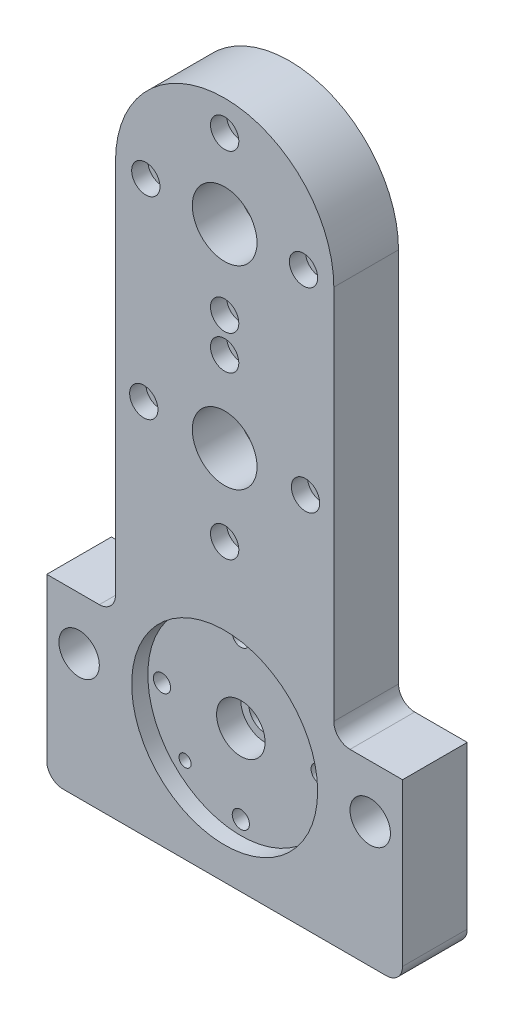
SolidWorks part; units mm, degrees
note: '?' marks a value the reader was unsure of.
material "6061 Alloy"
ref_plane "Front" through (0, 0, 0) normal (0, 0, 1) x (1, 0, 0)
ref_plane "Top" through (0, 0, 0) normal (0, 1, 0) x (1, 0, 0)
ref_plane "Right" through (0, 0, 0) normal (1, 0, 0) x (0, 0, -1)
ref_axis "Axis" through (0, 0, -80.9) along (0, 0, 1)?
sketch "Bolt circle" plane through (0, 0, 0) normal (0, 0, 1) x (1, 0, 0)
  line L0 (0, 36.5125) -> (0, 25.4) construction
  line L1 (-42.8625, 76.2) -> (-42.8625, -77.7875)
  line L2 (0, 101.6) -> (0, 112.7125) construction
  line L3 (42.8625, 76.2) -> (42.8625, -77.7875)
  line L7 (42.8625, -77.7875) -> (69.85, -77.7875)
  line L12 (-42.8625, -77.7875) -> (-69.85, -77.7875)
  line L30 (69.85, -77.7875) -> (69.85, -147.6375)
  line L31 (69.85, -147.6375) -> (-69.85, -147.6375)
  line L34 (-69.85, -77.7875) -> (-69.85, -147.6375)
  line L35 (0, 0) -> (0, -147.6375) construction
  circle A0 centre (0, 0) radius 36.5125 construction
  circle A1 centre (0, 0) radius 25.4 construction
  circle A2 centre (0, 0) radius 30.9562 construction
  arc A3 (-42.8625, 76.2) -> (42.8625, 76.2) centre (0, 76.2) cw
  circle A4 centre (0, 76.2) radius 12.7
  circle A5 centre (0, 76.2) radius 36.5125 construction
  circle A6 centre (0, 76.2) radius 25.4 construction
  circle A7 centre (0, 0) radius 12.7
  circle A8 centre (0, -98.425) radius 36.5125 construction
  circle A9 centre (0, -98.425) radius 6.35
  circle A10 centre (0, 76.2) radius 30.9562 construction
  point P0 (0, -36.5125)
  point P7 (0, 30.9562)
  point P9 (0, -134.9375)
  point P20 (0, 107.1562)
  dimension "D1" = 73.025
  dimension "D2" = 50.8
  dimension "D3" = 69.85
  dimension "D12" = 139.7
  dimension "D5" = 26.9875
  dimension "D13" = 25.4
  dimension "D18" = 12.7
  dimension "D6" = 76.2
  dimension "D8" = 73.025
  dimension "D9" = 25.4
  dimension "D10" = 50.8
  dimension "D4" = 98.425
  dimension "D7" = 85.725
  dimension "D17" = 12.7
extrude "Base" add sketch "Bolt circle" along normal mid plane 25.4
hole_wizard "Structure tube connection counterbore" positions "Sketch15" profile "Sketch14" counterbore size "1/4" standard "Ansi Inch" end condition through all
sketch "Sketch15" plane through (0, 0, -12.7) normal (0, 0, -1) x (-1, 0, 0)
  circle A0 centre (0, -98.425) radius 30.9563 construction
  point P1 (0, -67.4688)
  dimension "D1" = 61.9125
sketch "Sketch14" plane through (0, -67.4688, -12.7) normal (1, 0, 0) x (0, 1, 0)
  line L0 (0, 0) -> (0, 25.4)
  line L1 (0, 25.4) -> (3.3782, 25.4)
  line L3 (3.3782, 25.4) -> (3.3782, 6.35)
  line L4 (3.3782, 6.35) -> (5.5562, 6.35)
  line L5 (5.5562, 6.35) -> (5.5562, 0)
  line L7 (5.5562, 0) -> (0, 0)
  line L11 (0, -6.35) -> (0, 107.95) construction
  dimension "Thru Hole Dia." = 6.7564
  dimension "Thru Hole Depth" = 25.4
  dimension "C'Bore Dia." = 11.1125
  dimension "C'Bore Depth" = 6.35
pattern_circular "Structure tube connection counterbore pattern" count 4 over 360 about axis through (0, -98.425, 0) along (0, 0, 1) of "Structure tube connection counterbore"
hole_wizard "Spindle connection counterbore" positions "Sketch11" profile "Sketch10" counterbore size "1/4" standard "Ansi Inch" end condition through all
sketch "Sketch11" plane through (0, 0, 12.7) normal (0, 0, 1) x (1, 0, 0)
  circle A0 centre (0, 0) radius 31.75 construction
  point P0 (0, 31.75)
  dimension "D1" = 63.5
sketch "Sketch10" plane through (0, 31.75, 12.7) normal (1, 0, 0) x (0, -1, 0)
  line L0 (0, 0) -> (0, 25.4)
  line L1 (0, 25.4) -> (3.3782, 25.4)
  line L3 (3.3782, 25.4) -> (3.3782, 6.35)
  line L4 (3.3782, 6.35) -> (5.5562, 6.35)
  line L5 (5.5562, 6.35) -> (5.5562, 0)
  line L7 (5.5562, 0) -> (0, 0)
  line L11 (0, -6.35) -> (0, 107.95) construction
  dimension "Thru Hole Dia." = 6.7564
  dimension "Thru Hole Depth" = 25.4
  dimension "C'Bore Dia." = 11.1125
  dimension "C'Bore Depth" = 6.35
pattern_circular "Spindle connection counterbore pattern" count 4 over 360 about axis through (0, 0, 0) along (0, 0, 1) of "Spindle connection counterbore"
sketch "Sketch16" plane through (0, 0, 12.7) normal (0, 0, 1) x (1, 0, 0)
  circle A0 centre (0, -98.425) radius 36.5125
  dimension "D1" = 73.025
extrude "Structure tube mounting pocket" cut sketch "Sketch16" against normal blind 6.35
sketch "Sketch17" plane through (0, 0, -12.7) normal (0, 0, -1) x (-1, 0, 0)
  circle A0 centre (0, 0) radius 36.5125
  circle A1 centre (0, -98.425) radius 36.5125 construction
  dimension "D1" = 73.025
extrude "Spindle mounting pocket" cut sketch "Sketch17" against normal blind 7.62
sketch "Sketch18" plane through (0, 0, 6.35) normal (0, 0, 1) x (1, 0, 0)
  circle A0 centre (0, -98.425) radius 9.525
  dimension "D1" = 19.05
extrude "Lead screw through hole" cut sketch "Sketch18" against normal blind 9.525
sketch "Sketch20" plane through (0, 0, 12.7) normal (0, 0, 1) x (1, 0, 0)
  line L1 (57.15, -98.425) -> (-57.15, -98.425) construction
  circle A0 centre (57.15, -98.425) radius 7.9375
  circle A1 centre (-57.15, -98.425) radius 7.9375
  dimension "D2" = 114.3
  dimension "D3" = 15.875
extrude "Rail mounting pilot_holes" cut sketch "Sketch20" against normal through all
sketch "Sketch27" plane through (0, 0, 6.35) normal (0, 0, 1) x (1, 0, 0)
  line L0 (20.6813, -74.3354) -> (19.6028, -75.5003)
  line L1 (24.176, -77.571) -> (23.0974, -78.7359)
  line L2 (21.8894, -76.5356) -> (-21.8894, -120.3144) construction
  line L3 (20.1421, -74.9178) -> (23.6367, -78.1534) construction
  line L4 (50, 0) -> (-50, 0) construction
  circle A0 centre (-21.8894, -120.3144) radius 2.3813
  arc A1 (24.176, -77.571) -> (20.6813, -74.3354) centre (22.4286, -75.9532) ccw
  arc A2 (23.0974, -78.7359) -> (19.6028, -75.5003) centre (21.3501, -77.1181) cw
  circle A3 centre (21.8894, -76.5356) radius 2.3813 construction
  circle A4 centre (0, -98.425) radius 30.9563 construction
  point P10 (20.1421, -74.9178)
  dimension "D2" = 45
  dimension "D3" = 4.7625
  dimension "D1" = 1.5875
extrude "Alignment_features" cut sketch "Sketch27" against normal blind 6.35
fillet "Generic_rounding_fillet" radius 6.35 4 edges at (42.8625, -77.7875, 0) (-42.8625, -77.7875, 0) (-69.85, -147.6375, 0) (69.85, -147.6375, 0)
sketch "Sketch21" plane through (0, -147.6375, 0) normal (0, -1, 0) x (1, 0, 0)
  line L0 (69.85, 0) -> (-69.85, 0) construction
  line L1 (69.85, 12.7) -> (69.85, -12.7) construction
  line L2 (-69.85, 12.7) -> (-69.85, -12.7) construction
  line L3 (0, -12.7) -> (0, 12.7) construction
  line L4 (-63.5, -12.7) -> (63.5, -12.7) construction
  line L5 (-63.5, 12.7) -> (63.5, 12.7) construction
  circle A0 centre (57.15, 0) radius 4.7625
  circle A1 centre (-57.15, 0) radius 4.7625
  dimension "D1" = 9.525
  dimension "D2" = 114.3
extrude "Point_mount_bores" [suppressed] cut sketch "Sketch21" against normal blind 6.35
sketch "Sketch22" plane through (0, 0, 12.7) normal (0, 0, 1) x (1, 0, 0)
  line L0 (69.85, -77.7875) -> (49.2125, -77.7875) construction
  line L1 (56.7531, -77.7875) -> (57.5469, -77.7875)
  line L2 (56.7531, -77.7875) -> (56.7531, -111.125)
  line L3 (57.15, -111.125) -> (57.15, -98.425) construction
  line L4 (57.5469, -77.7875) -> (57.5469, -111.125)
  line L5 (0, -147.6375) -> (0, 119.0625) construction
  line L6 (-63.5, -147.6375) -> (63.5, -147.6375) construction
  line L7 (-57.15, -111.125) -> (-57.15, -98.425) construction
  line L8 (-57.5469, -77.7875) -> (-57.5469, -111.125)
  line L9 (-56.7531, -77.7875) -> (-56.7531, -111.125)
  line L10 (-56.7531, -77.7875) -> (-57.5469, -77.7875)
  arc A0 (56.7531, -111.125) -> (57.5469, -111.125) centre (57.15, -111.125) ccw
  arc A2 (-56.7531, -111.125) -> (-57.5469, -111.125) centre (-57.15, -111.125) cw
  arc A3 (42.8625, 76.2) -> (-42.8625, 76.2) centre (0, 76.2) ccw construction
  dimension "D1" = 0.7937
  dimension "D2" = 12.7
extrude "Flexure_clamp_slits" [suppressed] cut sketch "Sketch22" against normal through all
hole_wizard "Flexure_clamp_counterbore" [suppressed] positions "Sketch24" profile "Sketch23" counterbore size "1/4" standard "Ansi Inch"
sketch "Sketch24" plane through (69.85, 0, 0) normal (1, 0, 0) x (0, 0, -1)
  line L0 (0, 50) -> (0, -50) construction
  line L1 (-12.7, -77.7875) -> (12.7, -77.7875) construction
  point P0 (0, -85.725)
  dimension "D1" = 7.9375
sketch "Sketch23" plane through (69.85, -85.725, 0) normal (0, 1, 0) x (0, 0, -1)
  line L0 (0, 0) -> (0, 12.3031)
  line L1 (0, 12.3031) -> (3.3782, 12.3031)
  line L3 (3.3782, 12.3031) -> (3.3782, 6.35)
  line L4 (3.3782, 6.35) -> (5.5562, 6.35)
  line L5 (5.5562, 6.35) -> (5.5562, 0)
  line L7 (5.5562, 0) -> (0, 0)
  line L11 (0, -6.35) -> (0, 107.95) construction
  dimension "Thru Hole Dia." = 6.7564
  dimension "Thru Hole Depth" = 12.3031
  dimension "C'Bore Dia." = 11.1125
  dimension "C'Bore Depth" = 6.35
hole_wizard "Flexure_clamp_threads" [suppressed] positions "Sketch26" profile "Sketch25" tap size "1/4-20" standard "Ansi Inch"
sketch "Sketch26" [suppressed] plane through (56.7531, 0, 0) normal (1, 0, 0) x (0, 0, -1)
  point P1 (0, -85.725)
sketch "Sketch25" plane through (56.7531, -85.725, 0) normal (0, 1, 0) x (0, 0, -1)
  line L0 (0, 0) -> (0, 18.0438)
  line L1 (0, 18.0438) -> (2.5527, 16.51)
  line L2 (2.5527, 16.51) -> (2.5527, 0)
  line L5 (2.5527, 0) -> (0, 0)
  line L10 (0, 18.0438) -> (-2.5527, 16.51) construction
  line L11 (0, -6.35) -> (0, 107.95) construction
  dimension "Tap Drill Dia." = 5.1054
  dimension "Tap Drill Depth" = 16.51
  dimension "Drill Angle" = 118
cosmetic thread "Hole Thread2" [suppressed] parameters "D1"=12.7, "D2"=6.35
mirror "Flexure_clamp_fastener_holes" [suppressed] about plane through (0, 0, 0) normal (1, 0, 0)
hole_wizard "wood_spindle_CBORE" positions "Sketch28" profile "Sketch29" counterbore size "1/4" standard "ANSI Inch" end condition through all
sketch "Sketch28" plane through (0, 0, 12.7) normal (0, 0, 1) x (1, 0, 0)
  point P0 (0, 107.1562)
sketch "Sketch29" plane through (0, 107.1562, 12.7) normal (1, 0, 0) x (0, -1, 0)
  line L0 (0, 0) -> (0, 25.4)
  line L1 (0, 25.4) -> (3.3782, 25.4)
  line L3 (3.3782, 25.4) -> (3.3782, 6.35)
  line L4 (3.3782, 6.35) -> (5.5562, 6.35)
  line L5 (5.5562, 6.35) -> (5.5562, 0)
  line L7 (5.5562, 0) -> (0, 0)
  line L11 (0, -6.35) -> (0, 107.95) construction
  dimension "Thru Hole Dia." = 6.7564
  dimension "Thru Hole Depth" = 25.4
  dimension "C'Bore Dia." = 11.1125
  dimension "C'Bore Depth" = 6.35
pattern_circular "CirPattern1" count 4 over 360 about axis through (0, 76.2, 0) along (0, 0, 1) of "wood_spindle_CBORE"
sketch "Sketch30" plane through (0, 0, -12.7) normal (0, 0, -1) x (-1, 0, 0)
  circle A0 centre (0, 76.2) radius 36.5125
  dimension "D1" = 73.025
extrude "Cut-Extrude1" cut sketch "Sketch30" against normal blind 7.62
